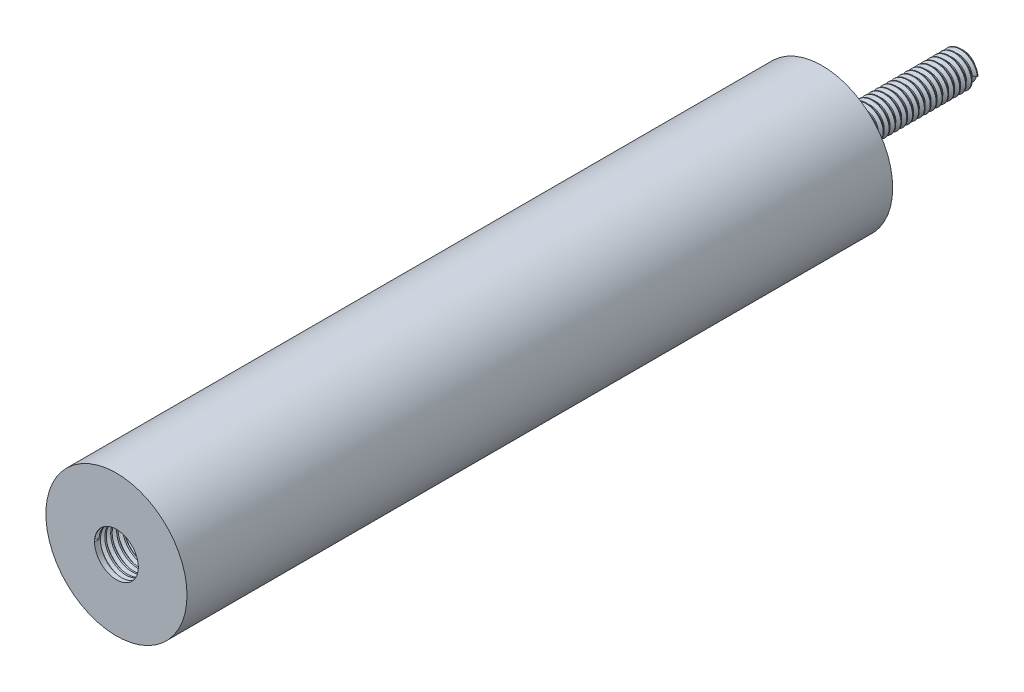
SolidWorks part; units mm, degrees
ref_plane "Front Plane" through (0, 0, 0) normal (0, 0, 1) x (1, 0, 0)
ref_plane "Top Plane" through (0, 0, 0) normal (0, 1, 0) x (1, 0, 0)
ref_plane "Right Plane" through (0, 0, 0) normal (1, 0, 0) x (0, 0, -1)
sketch "Sketch1" plane through (0, 0, 0) normal (0, 0, 1) x (1, 0, 0)
  line L1 (0, 0) -> (25.4, 0)
  line L2 (0, 0) -> (0, 32.766)
  line L3 (0, 32.766) -> (25.4, 32.766)
  line L4 (25.4, 0) -> (25.4, 32.766)
  dimension "D1" = 25.4
  dimension "D2" = 32.766
extrude "Boss-Extrude1" add sketch "Sketch1" against normal blind 127
sketch "Sketch2" plane through (0, 0, 0) normal (0, 0, 1) x (1, 0, 0)
  line L0 (25.4, 32.766) -> (0, 32.766) construction
  line L1 (25.4, 0) -> (25.4, 32.766) construction
  line L3 (0, 32.766) -> (25.4, 32.766)
  line L4 (0, 32.766) -> (0, 0)
  line L5 (0, 0) -> (25.4, 0)
  line L6 (25.4, 32.766) -> (25.4, 0)
  circle A0 centre (12.7, 16.383) radius 2.4574
  dimension "D1" = 4.9149
  dimension "D2" = 16.383
  dimension "D3" = 12.7
extrude "Cut-Extrude2" cut sketch "Sketch2" against normal blind 25.4
sketch "Sketch5" plane through (0, 0, -25.4) normal (0, 0, 1) x (1, 0, 0)
  line L0 (25.4, 32.766) -> (0, 32.766) construction
  line L1 (25.4, 0) -> (25.4, 32.766) construction
  line L3 (0, 32.766) -> (25.4, 32.766)
  line L4 (0, 32.766) -> (0, 0)
  line L5 (0, 0) -> (25.4, 0)
  line L6 (25.4, 32.766) -> (25.4, 0)
  circle A0 centre (12.7, 16.383) radius 12.7
  line M1 (0, 32.766) -> (0, 0)
  line M2 (0, 0) -> (25.4, 0)
  line M3 (25.4, 0) -> (25.4, 32.766)
  line M4 (25.4, 32.766) -> (0, 32.766)
  dimension "D1" = 16.383
  dimension "D3" = 25.4
  dimension "D2" = 12.7
extrude "Cut-Extrude3" cut sketch "Sketch5" against normal up to surface (101.6 mm away) contours A0 L6 M4 M1 | A0 L4 M2 M3 region at (12.7, 32.4637, -25.4) region at (12.7, 3.3807, -25.4) up to face at (12.7, 16.383, -127)
sketch "Sketch7" plane through (0, 0, -127) normal (0, 0, -1) x (-1, 0, 0)
  circle A0 centre (-12.7, 16.383) radius 2.413
  dimension "D1" = 4.826
extrude "Boss-Extrude2" add sketch "Sketch7" along normal blind 25.4
thread "Thread3" pitch 1.0583 method extrude profile "Thread Profile3" start angle 0, offset 0, length 0, pitch 1.0583, diameter 4.826
ref_plane "Plane4" through (15.113, 16.383, -152.4) normal (0, -1, 0) x (1, 0, 0)
sketch "Thread Profile3" plane through (15.113, 16.383, -152.4) normal (0, -1, 0) x (1, 0, 0)
  line L0 (0, 0) -> (0, 1.0583) construction
  line L1 (0, 0) -> (0.5728, 0.3307)
  line L2 (0.5728, 0.3307) -> (0.5728, 0.463)
  line L3 (0.5728, 0.463) -> (0, 0.7937)
  line L4 (0.5728, 0.3969) -> (0, 0.3969) construction
  line L11 (0, 0) -> (0, 0.7937)
  point P2 (0, 0)
  dimension "Pitch" = 1.0583
  dimension "Profile_Angle" = 60
  dimension "Profile_Land" = 0.1323
  dimension "Profile_Height" = 0.5728
sketch "Sketch10" plane through (0, 0, -25.4) normal (0, 0, 1) x (1, 0, 0)
  circle A0 centre (12.7, 16.383) radius 12.7
  dimension "D1" = 25.4
extrude "Boss-Extrude3" add sketch "Sketch10" along normal blind 25.4
sketch "Sketch11" plane through (0, 0, 0) normal (0, 0, 1) x (1, 0, 0)
  circle A0 centre (12.7, 16.383) radius 3.937
  dimension "D1" = 7.874
extrude "Cut-Extrude4" cut sketch "Sketch11" against normal blind 12.7
thread "Thread4" pitch 1.0583 method cut profile "Thread Profile4" start angle 0, offset 0, length 0, pitch 1.0583, diameter 7.874
ref_plane "Plane5" through (8.763, 16.383, 0) normal (0, -1, 0) x (-1, 0, 0)
sketch "Thread Profile4" plane through (8.763, 16.383, 0) normal (0, -1, 0) x (-1, 0, 0)
  line L0 (0, 0) -> (0, 1.0583) construction
  line L1 (0, 0) -> (0.5728, 0.3307)
  line L2 (0.5728, 0.3307) -> (0.5728, 0.463)
  line L3 (0.5728, 0.463) -> (0, 0.7937)
  line L4 (0.5728, 0.3969) -> (0, 0.3969) construction
  line L11 (0, 0) -> (0, 0.7937)
  point P2 (0, 0)
  dimension "Pitch" = 1.0583
  dimension "Profile_Angle" = 60
  dimension "Profile_Land" = 0.1323
  dimension "Profile_Height" = 0.5728
